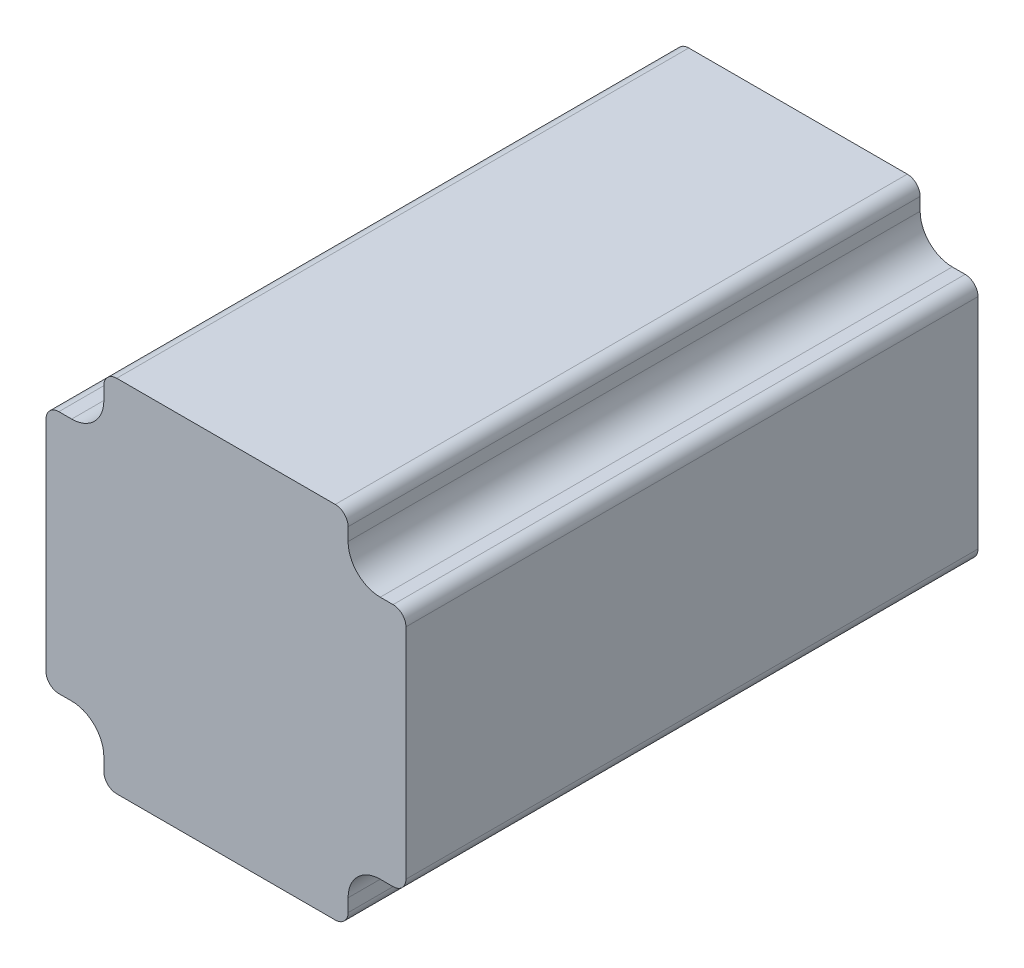
SolidWorks part; units mm, degrees
ref_plane "Front Plane" through (0, 0, 0) normal (0, 0, 1) x (1, 0, 0)
ref_plane "Top Plane" through (0, 0, 0) normal (0, 1, 0) x (1, 0, 0)
ref_plane "Right Plane" through (0, 0, 0) normal (1, 0, 0) x (0, 0, -1)
sketch "Sketch1" plane through (0, 0, 0) normal (0, 0, 1) x (1, 0, 0)
  line L1 (28, -28) -> (-28, -28)
  line L2 (28, -28) -> (28, 28)
  line L3 (28, 28) -> (-28, 28)
  line L4 (-28, -28) -> (-28, 28)
  line L5 (28, -28) -> (-28, 28) construction
  line L6 (28, 28) -> (-28, -28) construction
  point P0 (0, 0)
  dimension "D1" = 56
  dimension "D2" = 56
extrude "Boss-Extrude1" add sketch "Sketch1" along normal blind 89
sketch "Sketch2" plane through (0, 0, 89) normal (0, 0, 1) x (1, 0, 0)
  line L0 (19, 28) -> (19, 19)
  line L1 (28, 28) -> (-28, 28) construction
  line L2 (19, 19) -> (28, 19)
  line L3 (28, -28) -> (28, 28) construction
  line L4 (28, 19) -> (28, 28)
  line L5 (28, 28) -> (19, 28)
  dimension "D1" = 9
  dimension "D2" = 9
extrude "Cut-Extrude1" cut sketch "Sketch2" against normal blind 89
ref_axis "Axis1" through (0, 0, -4.45) along (0, 0, 1)
pattern_circular "CirPattern1" count 4 over 360 about axis through (0, 0, -4.45) along (0, 0, 1) of "Cut-Extrude1"
fillet "Fillet1" radius 5 4 edges at (19, 19, 44.5) (-19, 19, 44.5) (-19, -19, 44.5) (19, -19, 44.5)
fillet "Fillet2" radius 2 8 edges at (19, 28, 44.5) (28, 19, 44.5) (28, -19, 44.5) (19, -28, 44.5) (-19, -28, 44.5) (-28, -19, 44.5) (-28, 19, 44.5) (-19, 28, 44.5)
